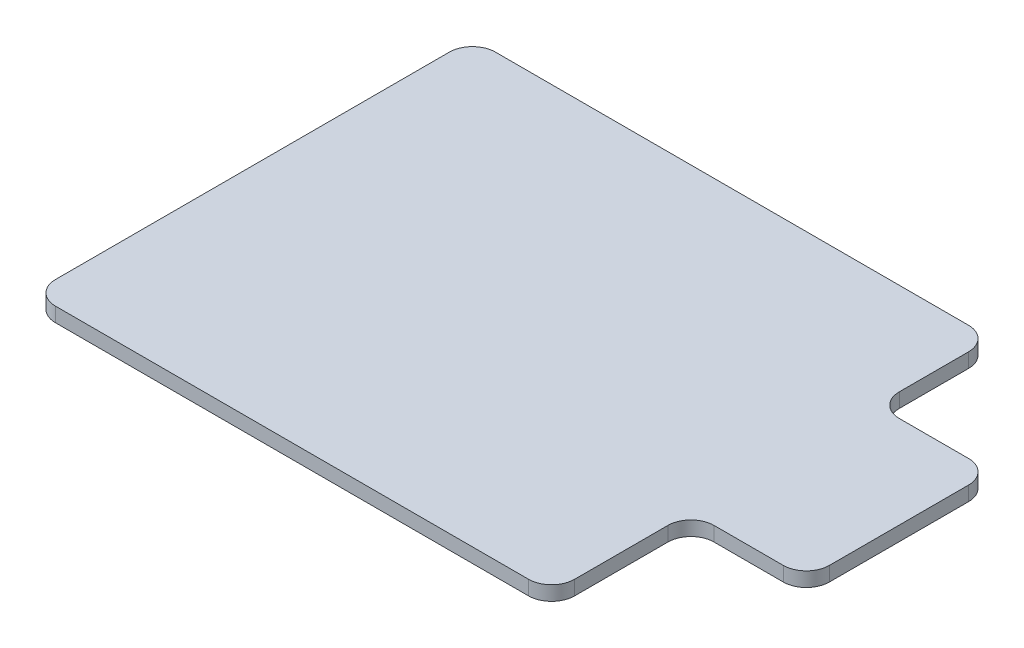
SolidWorks part; units mm, degrees
material "AISI Type A2 Tool Steel"
ref_plane "Front Plane" through (0, 0, 0) normal (0, 0, 1) x (1, 0, 0)
ref_plane "Top Plane" through (0, 0, 0) normal (0, 1, 0) x (1, 0, 0)
ref_plane "Right Plane" through (0, 0, 0) normal (1, 0, 0) x (0, 0, -1)
sketch "Sketch1" plane through (0, 0, 0) normal (0, 1, 0) x (1, 0, 0)
  point P0 (0, 0)
  line B0 (0, 0) -> (0, -48.4323)
  line B1 (0, -48.4323) -> (57.15, -48.4323)
  line B2 (57.15, -48.4323) -> (57.15, -33.0905)
  line B3 (57.15, -33.0905) -> (69.85, -33.0905)
  line B4 (69.85, -33.0905) -> (69.85, -12.7)
  line B5 (69.85, -12.7) -> (57.15, -12.7)
  line B6 (57.15, -12.7) -> (57.15, 0)
  line B7 (0, 0) -> (57.15, 0)
sketch_block_instance "Block-Armor-1"
sketch_block "Block-Armor" parameters "D1"=12.7
extrude "Boss-Extrude1" add sketch "Sketch1" along normal blind 1.5875
fillet "Fillet1" radius 2.54 8 edges at (0, 0.7937, 48.4323) (0, 0.7937, 0) (57.15, 0.7937, 0) (57.15, 0.7937, 48.4323) (69.85, 0.7937, 33.0905) (69.85, 0.7937, 12.7) (57.15, 0.7937, 33.0905) (57.15, 0.7937, 12.7)
